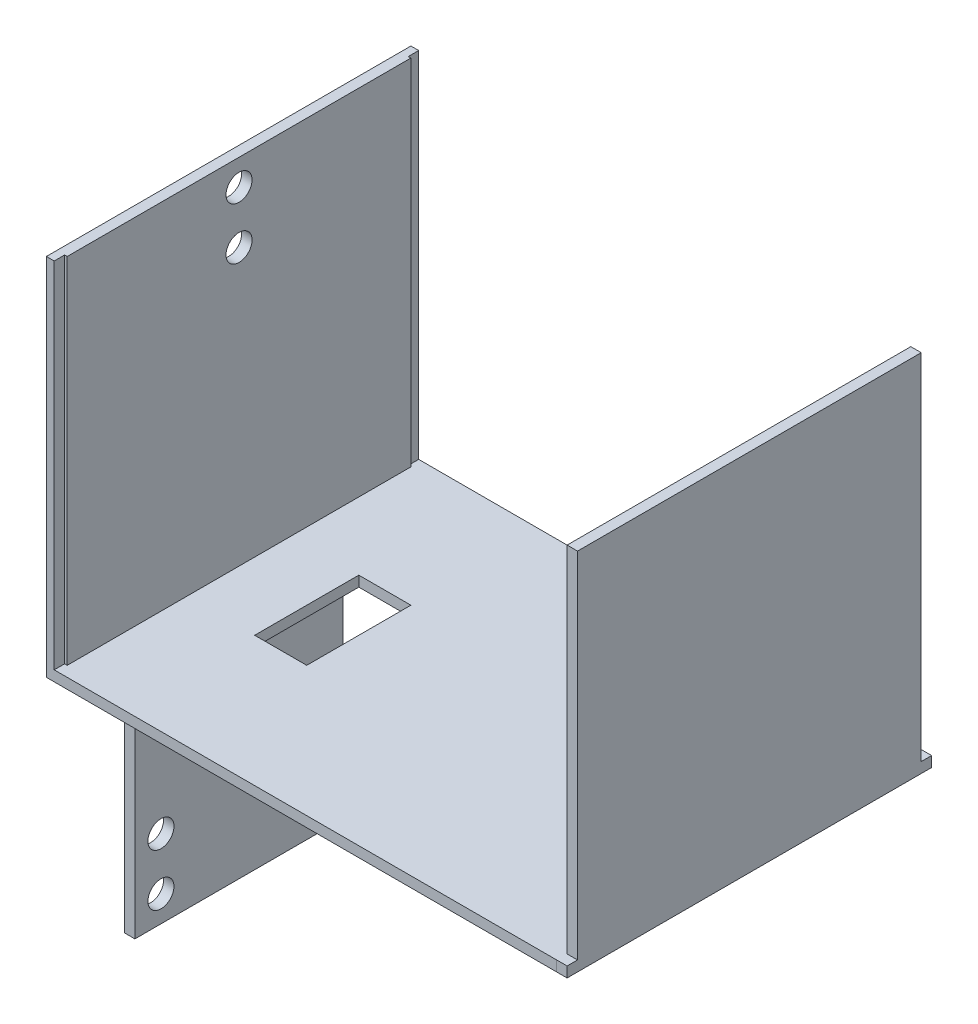
SolidWorks part; units mm, degrees
ref_plane "Front Plane" through (0, 0, 0) normal (0, 0, 1) x (1, 0, 0)
ref_plane "Top Plane" through (0, 0, 0) normal (0, 1, 0) x (1, 0, 0)
ref_plane "Right Plane" through (0, 0, 0) normal (1, 0, 0) x (0, 0, -1)
sketch "Sketch1" plane through (0, 0, 0) normal (0, 0, 1) x (1, 0, 0)
  line L0 (1.8944, 59.1392) -> (1.8944, -10.8608) construction
  line L1 (-48.1056, 59.1392) -> (51.8944, 59.1392)
  line L2 (-48.1056, 59.1392) -> (-48.1056, -10.8608)
  line L3 (-48.1056, -10.8608) -> (51.8944, -10.8608)
  line L4 (51.8944, 59.1392) -> (51.8944, -10.8608)
  line L5 (-48.1056, 24.1392) -> (51.8944, 24.1392) construction
  circle A0 centre (-23.1056, 9.1392) radius 14
  circle A1 centre (-23.1056, 39.1392) radius 14
  circle A2 centre (26.8944, 9.1392) radius 14
  circle A3 centre (26.8944, 39.1392) radius 14
  dimension "D3" = 28
  dimension "D1" = 70
  dimension "D2" = 100
  dimension "D4" = 15
  dimension "D5" = 25
extrude "Body" add sketch "Sketch1" along normal blind 70 contours A1 | A0 | A3 | A2 | L4 L1 L2 L3 A3 A1 A0 A2 region at (1.8944, 24.1392, 0) region at (-23.1056, 9.1392, 0) region at (-23.1056, 39.1392, 0) region at (26.8944, 9.1392, 0) region at (26.8944, 39.1392, 0)
extrude "Front Btns" cut sketch "Sketch1<3>" along normal blind 10 contours A2 | A0 region at (-23.1056, 9.1392, 0) region at (26.8944, 9.1392, 0)
sketch "Sketch1<3>" plane through (0, 0, 0) normal (0, 0, 1) x (1, 0, 0) same geometry as "Sketch1"
extrude "Back Btns" cut sketch "Sketch1<4>" against normal blind 10 from surface contours A3 | A1 region at (-23.1056, 39.1392, 0) region at (26.8944, 39.1392, 0) starting at face at (1.8944, 24.1392, 70)
sketch "Sketch1<4>" plane through (0, 0, 0) normal (0, 0, 1) x (1, 0, 0) same geometry as "Sketch1"
sketch "Sketch2" plane through (0, 0, 0) normal (0, 0, -1) x (-1, 0, 0)
  line L0 (-1.8944, 59.1392) -> (-1.8944, -10.8608) construction
  line L1 (48.1056, 59.1392) -> (-51.8944, 59.1392) construction
  line L2 (48.1056, -10.8608) -> (-51.8944, -10.8608) construction
  circle A0 centre (-1.8944, 8.3773) radius 3.4
  dimension "D1" = 6.8
extrude "Potentiometer" cut sketch "Sketch2" against normal blind 10
sketch "Sketch3" plane through (0, 59.1392, 0) normal (0, 1, 0) x (1, 0, 0)
  line L0 (51.8944, -70) -> (51.8944, 0) construction
  line L1 (49.8944, -68) -> (-46.1056, -68)
  line L2 (49.8944, -68) -> (49.8944, -2)
  line L3 (49.8944, -2) -> (-46.1056, -2)
  line L4 (-46.1056, -68) -> (-46.1056, -2)
  line L5 (-48.1056, -70) -> (-48.1056, 0) construction
  line L6 (-48.1056, 0) -> (51.8944, 0) construction
  line L7 (-48.1056, -70) -> (51.8944, -70) construction
  dimension "D1" = 2
  dimension "D2" = 2
  dimension "D3" = 2
  dimension "D4" = 2
extrude "Internals" cut sketch "Sketch3" against normal blind 68
sketch "Sketch5" plane through (0, -10.8608, 0) normal (0, -1, 0) x (1, 0, 0)
  line L0 (51.8944, 35) -> (-48.1056, 35) construction
  line L1 (-23.1056, 25) -> (-33.1056, 25)
  line L2 (-23.1056, 25) -> (-23.1056, 45)
  line L3 (-23.1056, 45) -> (-33.1056, 45)
  line L4 (-33.1056, 25) -> (-33.1056, 45)
  line L5 (51.8944, 70) -> (51.8944, 0) construction
  line L6 (-48.1056, 70) -> (-48.1056, 0) construction
  line L7 (-23.1056, 35) -> (-33.1056, 35) construction
  line L8 (-28.1056, 25) -> (-28.1056, 45) construction
  dimension "D1" = 20
  dimension "D2" = 10
  dimension "D3" = 20
extrude "USB+Cable Port" cut sketch "Sketch5" against normal blind 10
sketch "Sketch6" plane through (0, -10.8608, 0) normal (0, -1, 0) x (1, 0, 0)
  line L0 (-48.1056, 70) -> (-48.1056, 0) construction
  line L1 (-48.1056, 15) -> (-46.1056, 15)
  line L2 (-48.1056, 15) -> (-48.1056, 55)
  line L3 (-48.1056, 55) -> (-46.1056, 55)
  line L4 (-46.1056, 15) -> (-46.1056, 55)
  line L5 (-46.1056, 35) -> (-48.1056, 35) construction
  line L6 (-34.1056, 35) -> (-38.9546, 35) construction
  line L7 (-34.1056, 15) -> (-36.1056, 15)
  line L8 (-34.1056, 15) -> (-34.1056, 55)
  line L9 (-34.1056, 55) -> (-36.1056, 55)
  line L10 (-36.1056, 15) -> (-36.1056, 55)
  line L11 (51.8944, 35) -> (-48.1056, 35) construction
  line L12 (51.8944, 70) -> (51.8944, 0) construction
  dimension "D1" = 40
  dimension "D2" = 2
  dimension "D3" = 40
  dimension "D4" = 2
  dimension "D5" = 10
extrude "Mount" add sketch "Sketch6" along normal blind 50 contours L4 L3 L2 L1
sketch "Sketch7" plane through (-48.1056, 0, 0) normal (-1, 0, 0) x (0, 0, 1)
  line L0 (55, -60.8608) -> (15, -60.8608) construction
  line L1 (15, -60.8608) -> (15, -10.8608) construction
  line L2 (35, -60.8608) -> (35, -9.9157) construction
  circle A0 centre (20, -55.8608) radius 2.5
  circle A2 centre (20, -45.8608) radius 2.5
  circle A4 centre (50, -55.8608) radius 2.5
  circle A5 centre (50, -45.8608) radius 2.5
  dimension "D1" = 5
  dimension "D3" = 5
  dimension "D5" = 5
  dimension "D6" = 5
  dimension "D7" = 5
  dimension "D8" = 10
extrude "Mount To Trash" cut sketch "Sketch7" against normal blind 50
sketch "Sketch8" plane through (-48.1056, 0, 0) normal (-1, 0, 0) x (0, 0, 1)
  line L0 (35, 59.1392) -> (35, -60.8608) construction
  line L1 (70, 59.1392) -> (0, 59.1392) construction
  line L2 (55, -60.8608) -> (15, -60.8608) construction
  line L3 (1.75, 59.1392) -> (1.3, 57.3392)
  line L4 (1.3, 57.3392) -> (3.7, 57.3392)
  line L5 (3.7, 57.3392) -> (3.25, 59.1392)
  line L6 (0, 59.1392) -> (0, -10.8608) construction
  line L7 (68.25, 59.1392) -> (68.7, 57.3392)
  line L8 (68.7, 57.3392) -> (66.3, 57.3392)
  line L9 (66.3, 57.3392) -> (66.75, 59.1392)
  line L10 (1.75, 59.1392) -> (3.25, 59.1392)
  line L11 (66.75, 59.1392) -> (68.25, 59.1392)
  circle A0 centre (35, 54.1392) radius 2.5
  circle A1 centre (35, 44.1392) radius 2.5
  dimension "D6" = 5
  dimension "D7" = 5
  dimension "D1" = 1.5
  dimension "D2" = 2.4
  dimension "D3" = 1.8
  dimension "D4" = 0.45
  dimension "D5" = 1.3
  dimension "D8" = 5
  dimension "D9" = 10
sketch "Sketch9" plane through (51.8944, 0, 0) normal (1, 0, 0) x (0, 0, -1)
  line L0 (-70, 59.1392) -> (0, 59.1392) construction
  line L1 (-5, 59.1392) -> (-65, 59.1392)
  line L2 (-5, 59.1392) -> (-5, -9.8608)
  line L3 (-5, -9.8608) -> (-65, -9.8608)
  line L4 (-65, 59.1392) -> (-65, -9.8608)
  line L6 (0, 59.1392) -> (0, -10.8608) construction
  line L7 (-70, 59.1392) -> (-70, -10.8608) construction
  line L8 (-70, -10.8608) -> (0, -10.8608) construction
  dimension "D1" = 5
  dimension "D2" = 5
  dimension "D3" = 1
extrude "Mount Camera" cut sketch "Sketch8" against normal blind 5 contours L0 A0 | A0 L0 | L0 A1 | A1 L0 region at (-48.1056, 54.1392, 36.061) region at (-48.1056, 44.1392, 36.061) region at (-48.1056, 44.1392, 33.939) region at (-48.1056, 54.1392, 33.939)
sketch "Sketch10" plane through (0, 59.1392, 0) normal (0, 1, 0) x (1, 0, 0)
  line L0 (49.8944, 0) -> (49.8944, -70)
  line L1 (-48.1056, 0) -> (51.8944, 0) construction
  line L2 (-48.1056, -70) -> (51.8944, -70) construction
  line L3 (51.8944, -70) -> (51.8944, 0) construction
  dimension "D1" = 2
split line "Split Line1"
sketch "Sketch12" plane through (51.8944, 0, 0) normal (1, 0, 0) x (0, 0, -1)
  line L0 (-35, -10.8608) -> (-35, 59.1392) construction
  line L1 (0, 59.1392) -> (-2, 59.1392)
  line L2 (0, 59.1392) -> (0, -8.8608)
  line L3 (0, -8.8608) -> (-2, -8.8608)
  line L4 (-2, 59.1392) -> (-2, -8.8608)
  line L5 (-70, -10.8608) -> (0, -10.8608) construction
  line L6 (-70, 59.1392) -> (-68, 59.1392)
  line L7 (-70, -8.8608) -> (-68, -8.8608)
  line L8 (-70, 59.1392) -> (-70, -8.8608)
  line L9 (-68, 59.1392) -> (-68, -8.8608)
  dimension "D1" = 68
  dimension "D2" = 2
extrude "Cut-Extrude10" cut sketch "Sketch12" against normal blind 98.5
